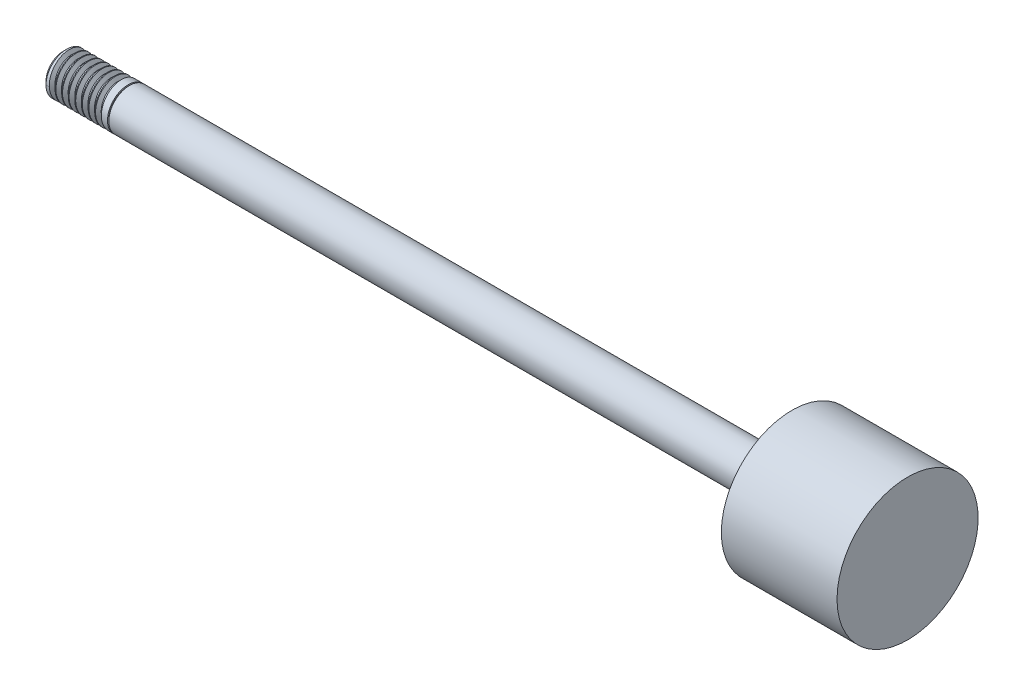
SolidWorks part; units mm, degrees
ref_plane "Front Plane" through (0, 0, 0) normal (0, 0, 1) x (1, 0, 0)
ref_plane "Top Plane" through (0, 0, 0) normal (0, 1, 0) x (1, 0, 0)
ref_plane "Right Plane" through (0, 0, 0) normal (1, 0, 0) x (0, 0, -1)
ref_plane "Plane1" through (0, 0, 0) normal (0, 0, -1) x (-1, 0, 0)
sketch "Sketch1" plane through (0, 0, 0) normal (0, 0, -1) x (-1, 0, 0)
  line L0 (-149.5044, 13.5572) -> (-149.5044, 0)
  line L1 (-149.5044, 0) -> (12.7, 0)
  line L2 (12.7, 0) -> (12.7, 3.3388)
  line L3 (12.7, 3.3388) -> (12.0701, 3.9688)
  line L4 (12.0701, 3.9688) -> (0.254, 3.9688)
  line L5 (0.254, 3.9688) -> (0.254, 3.7147)
  line L6 (0.254, 3.7147) -> (0, 3.7147)
  line L7 (0, 3.7147) -> (0, 3.9624)
  line L8 (0, 3.9624) -> (-127.2794, 3.9624)
  line L9 (-127.2794, 3.9624) -> (-127.2794, 13.5572)
  line L10 (-127.2794, 13.5572) -> (-149.5044, 13.5572)
  line L11 (-149.5044, 0) -> (12.7, 0) construction
revolve "Revolve1" add sketch "Sketch1" angle 360 about L11 reverse direction yes
thread "Thread1" pitch 1.27 method cut profile "Thread Profile1" start angle 0, offset 0, length 10, pitch 1.27, diameter 7.9375
ref_plane "Plane2" through (-12.0701, 0, -3.9688) normal (0, -1, 0) x (0, 0, -1)
sketch "Thread Profile1" plane through (-12.0701, 0, -3.9688) normal (0, -1, 0) x (0, 0, -1)
  line L0 (0, 0) -> (0, 1.27) construction
  line L11 (0, 0) -> (0, 1.1112)
  line L12 (0, 1.1112) -> (-0.6874, 0.7144)
  line L13 (-0.6874, 0.7144) -> (-0.6874, 0.3969)
  line L15 (-0.6874, 0.3969) -> (0, 0)
  line L17 (-0.6874, 0.5556) -> (0, 0.5556) construction
  point P2 (0, 0)
  dimension "Pitch" = 1.27
  dimension "Profile_Angle" = 60
  dimension "Profile_Land" = 0.3175
  dimension "Profile_Height" = 0.6874
